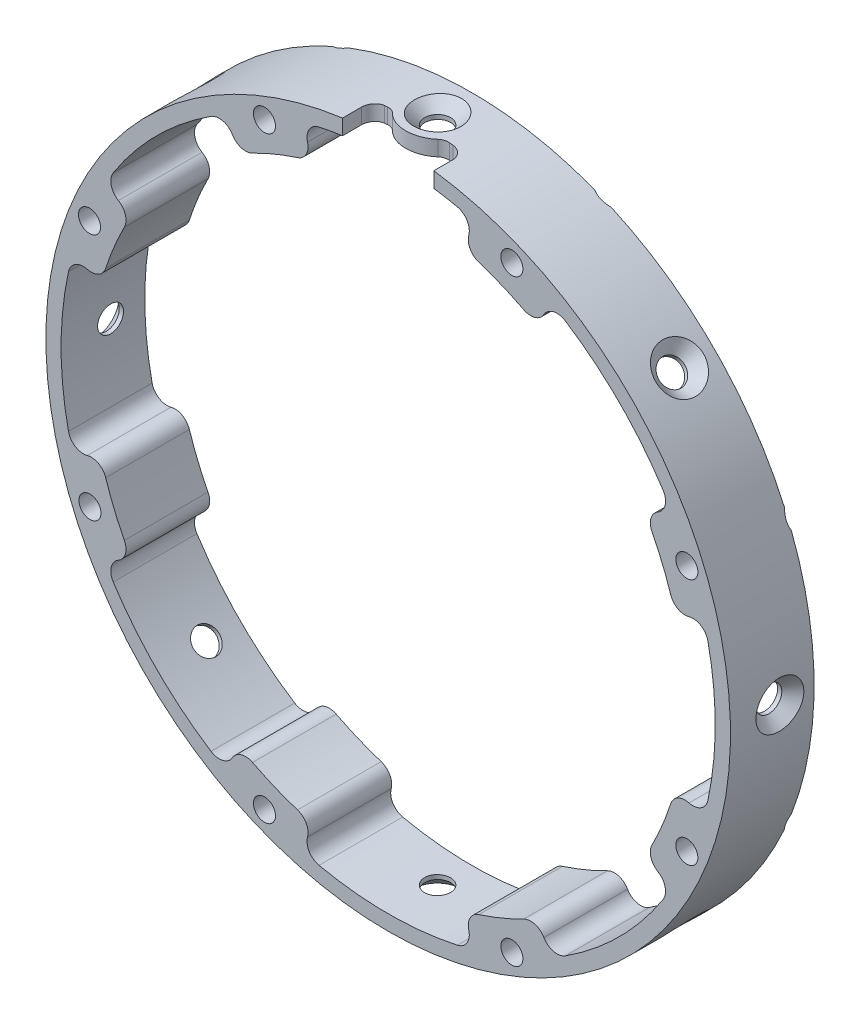
SolidWorks part; units mm, degrees
ref_plane "前视基准面" through (0, 0, 0) normal (0, 0, 1) x (1, 0, 0)
ref_plane "上视基准面" through (0, 0, 0) normal (0, 1, 0) x (1, 0, 0)
ref_plane "右视基准面" through (0, 0, 0) normal (1, 0, 0) x (0, 0, -1)
sketch "草图1" plane through (0, 0, 0) normal (0, 0, 1) x (1, 0, 0)
  line L0 (11.1292, 41.5348) -> (10.0939, 37.6711)
  line L17 (21.5, 37.2391) -> (19.5, 33.775)
  line L18 (-11.1292, 41.5348) -> (-10.0939, 37.6711)
  line L19 (37.2391, 21.5) -> (33.775, 19.5)
  line L20 (41.5348, 11.1292) -> (37.6711, 10.0939)
  line L21 (41.5348, -11.1292) -> (37.6711, -10.0939)
  line L22 (37.2391, -21.5) -> (33.775, -19.5)
  line L23 (21.5, -37.2391) -> (19.5, -33.775)
  line L24 (11.1292, -41.5348) -> (10.0939, -37.6711)
  line L25 (-11.1292, -41.5348) -> (-10.0939, -37.6711)
  line L26 (-21.5, -37.2391) -> (-19.5, -33.775)
  line L27 (-37.2391, -21.5) -> (-33.775, -19.5)
  line L28 (-41.5348, -11.1292) -> (-37.6711, -10.0939)
  line L29 (-41.5348, 11.1292) -> (-37.6711, 10.0939)
  line L30 (-37.2391, 21.5) -> (-33.775, 19.5)
  line L31 (-21.5, 37.2391) -> (-19.5, 33.775)
  circle A1 centre (0, 0) radius 45
  arc A3 (10.0939, 37.6711) -> (19.5, 33.775) centre (0, 0) cw
  arc A4 (11.1292, 41.5348) -> (-11.1292, 41.5348) centre (0, 0) ccw
  arc A21 (37.2391, 21.5) -> (21.5, 37.2391) centre (0, 0) ccw
  arc A22 (33.775, 19.5) -> (37.6711, 10.0939) centre (0, 0) cw
  arc A23 (41.5348, -11.1292) -> (41.5348, 11.1292) centre (0, 0) ccw
  arc A24 (37.6711, -10.0939) -> (33.775, -19.5) centre (0, 0) cw
  arc A25 (21.5, -37.2391) -> (37.2391, -21.5) centre (0, 0) ccw
  arc A26 (19.5, -33.775) -> (10.0939, -37.6711) centre (0, 0) cw
  arc A27 (-11.1292, -41.5348) -> (11.1292, -41.5348) centre (0, 0) ccw
  arc A28 (-10.0939, -37.6711) -> (-19.5, -33.775) centre (0, 0) cw
  arc A29 (-37.2391, -21.5) -> (-21.5, -37.2391) centre (0, 0) ccw
  arc A30 (-33.775, -19.5) -> (-37.6711, -10.0939) centre (0, 0) cw
  arc A31 (-41.5348, 11.1292) -> (-41.5348, -11.1292) centre (0, 0) ccw
  arc A32 (-37.6711, 10.0939) -> (-33.775, 19.5) centre (0, 0) cw
  arc A33 (-21.5, 37.2391) -> (-37.2391, 21.5) centre (0, 0) ccw
  arc A34 (-19.5, 33.775) -> (-10.0939, 37.6711) centre (0, 0) cw
  point P51 (0, 0)
  point P56 (0, 0)
  dimension "D1" = 8
extrude "凸台-拉伸1" add sketch "草图1" against normal blind 11
hole_wizard "M3 锥坑平头的锥孔2" positions "3D草图3" profile "草图4" countersink size "M3" standard "BSI" end condition through all
sketch3d "3D草图3"
  point P67 (31.8198, 31.8198, -6.5)
  point P76 (45, 0, -6.5)
  point P83 (31.8198, -31.8198, -6.5)
  point P85 (-31.8198, 31.8198, -6.5)
  point P87 (-31.8198, -31.8198, -6.5)
  point P96 (0, -45, -6.5)
  point P98 (0, 45, -6.5)
  point P105 (-45, 0, -6.5)
sketch "草图4" plane through (31.8198, 31.8198, -6.5) normal (0, 0, 1) x (-0.7071, 0.7071, 0)
  line L0 (0, 0) -> (0, 108.6396)
  line L1 (0, 108.6396) -> (1.7, 108.6396)
  line L2 (1.7, 108.6396) -> (1.7, 1.45)
  line L3 (1.7, 1.45) -> (3.15, 0)
  line L5 (3.15, 0) -> (0, 0)
  line L6 (-1.7, 1.45) -> (-3.15, 0) construction
  line L11 (0, -6.35) -> (0, 107.95) construction
  dimension "通孔孔直径" = 3.4
  dimension "通孔孔深度" = 108.6396
  dimension "近端锥形沉头孔直径" = 6.3
  dimension "近端锥形沉头孔角度" = 90
ref_plane "基准面1" through (0, 45, 0) normal (0, 1, 0) x (1, 0, 0)
sketch "草图7" plane through (0, 45, 0) normal (0, 1, 0) x (1, 0, 0)
  line L0 (-6, 0) -> (6, 0)
  line L1 (-45, 0) -> (45, 0) construction
  line L2 (6, 0) -> (6, 4)
  line L3 (6, 4) -> (3.3749, 4)
  line L5 (-6, 0) -> (-6, 4)
  line L6 (-6, 4) -> (-3.3749, 4)
  arc A1 (3.3749, 4) -> (-3.3749, 4) centre (0, 6.5) cw
extrude "切除-拉伸1" cut sketch "草图7" against normal up to next
hole_wizard "M2.5 锥坑平头的锥孔2" positions "3D草图4" profile "草图8" countersink size "M2.5" standard "BSI" end condition up to next
sketch3d "3D草图4"
  point P13 (39.2649, 16.264, -11)
  point P19 (16.264, 39.2649, -11)
  point P21 (-16.264, 39.2649, -11)
  point P23 (39.2649, -16.264, -11)
  point P26 (-39.2649, 16.264, -11)
  point P28 (-39.2044, -16.264, -11)
  point P30 (-16.264, -39.2649, -11)
  point P32 (16.264, -39.2649, -11)
  point P62 (0, 0, 0)
  point P63 (0, 0, 0)
  point P64 (0, 0, 0)
  point P65 (0, 0, 0)
  point P66 (0, 0, 0)
  point P67 (0, 0, 0)
  point P68 (0, 0, 0)
  point P69 (0, 0, 0)
  point P70 (0, 0, 0)
  point P71 (0, 0, 0)
  point P72 (0, 0, 0)
  point P73 (0, 0, 0)
  point P74 (0, 0, 0)
  point P75 (0, 0, 0)
  point P76 (0, 0, 0)
  point P77 (0, 0, 0)
  point P78 (0, 0, 0)
  point P79 (0, 0, 0)
  point P80 (0, 0, 0)
  point P81 (0, 0, 0)
  point P82 (0, 0, 0)
  point P83 (0, 0, 0)
  point P84 (0, 0, 0)
  point P85 (0, 0, 0)
sketch "草图8" plane through (39.2649, 16.264, -11) normal (1, 0, 0) x (0, 1, 0)
  line L0 (0, 0) -> (0, 11)
  line L1 (0, 11) -> (1.45, 11)
  line L2 (1.45, 11) -> (1.45, 1.3)
  line L3 (1.45, 1.3) -> (2.75, 0)
  line L5 (2.75, 0) -> (0, 0)
  line L6 (-1.45, 1.3) -> (-2.75, 0) construction
  line L11 (0, -6.35) -> (0, 107.95) construction
  dimension "通孔孔直径" = 2.9
  dimension "通孔孔深度" = 11
  dimension "近端锥形沉头孔直径" = 5.5
  dimension "近端锥形沉头孔角度" = 90
fillet "圆角1" radius 2 32 edges at (-41.5348, -11.1292, -5.5) (-37.6711, -10.0939, -5.5) (-33.775, -19.5, -5.5) (-37.2391, -21.5, -5.5) (-21.5, -37.2391, -5.5) (-10.0939, -37.6711, -5.5) (-19.5, -33.775, -5.5) (-11.1292, -41.5348, -5.5) (11.1292, -41.5348, -5.5) (10.0939, -37.6711, -5.5) (19.5, -33.775, -5.5) (21.5, -37.2391, -5.5) (37.2391, -21.5, -5.5) (33.775, -19.5, -5.5) (37.6711, -10.0939, -5.5) (41.5348, -11.1292, -5.5) (41.5348, 11.1292, -5.5) (37.6711, 10.0939, -5.5) (33.775, 19.5, -5.5) (37.2391, 21.5, -5.5) (21.5, 37.2391, -5.5) (11.1292, 41.5348, -5.5) (10.0939, 37.6711, -5.5) (19.5, 33.775, -5.5) (-11.1292, 41.5348, -5.5) (-10.0939, 37.6711, -5.5) (-21.5, 37.2391, -5.5) (-19.5, 33.775, -5.5) (-37.2391, 21.5, -5.5) (-33.775, 19.5, -5.5) (-37.6711, 10.0939, -5.5) (-41.5348, 11.1292, -5.5)
fillet "圆角2" radius 1.5 4 edges at (-6, 43.5888, -4) (6, 43.5888, -4) (-3.3749, 43.8703, -4) (3.3749, 43.8703, -4)
